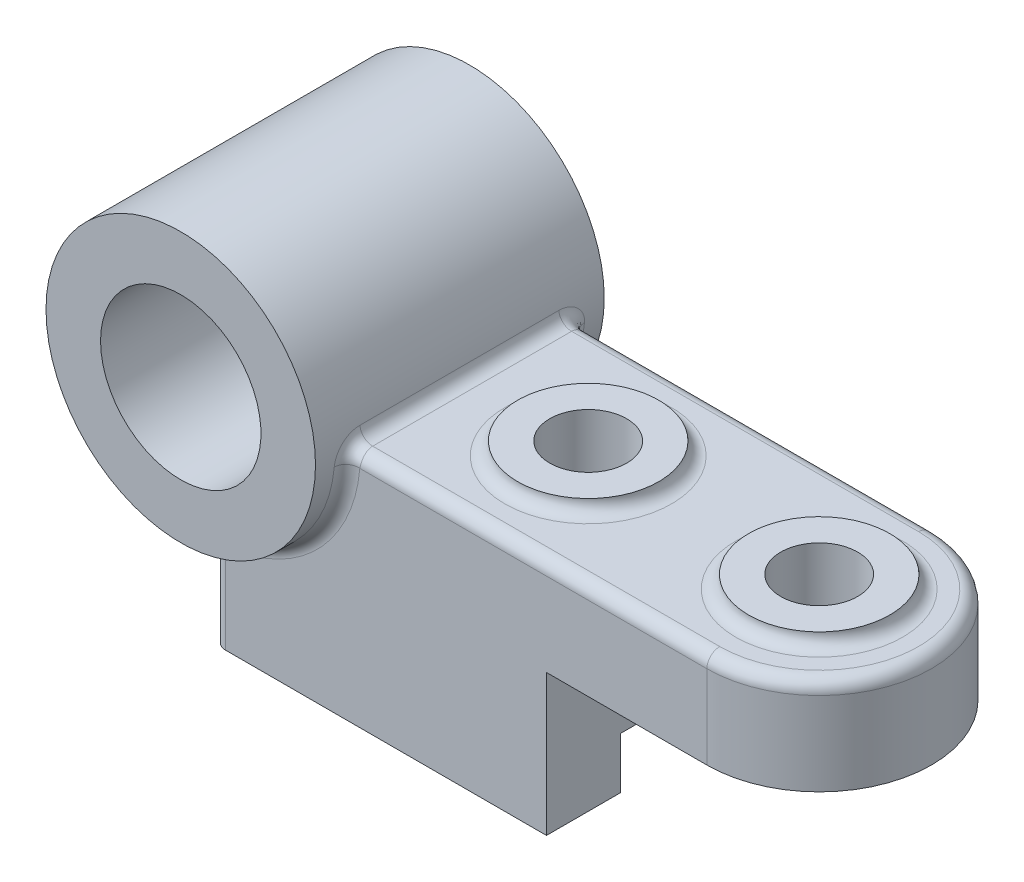
SolidWorks part; units mm, degrees
note: The reader was unsure of these and kept them because the rebuilt part matched: shared geometry of "Sketch1<3>", "Sketch2<3>".
ref_plane "Front Plane" through (0, 0, 0) normal (0, 0, 1) x (1, 0, 0)
ref_plane "Top Plane" through (0, 0, 0) normal (0, 1, 0) x (1, 0, 0)
ref_plane "Right Plane" through (0, 0, 0) normal (1, 0, 0) x (0, 0, -1)
sketch "Sketch1" plane through (0, 0, 0) normal (0, 0, 1) x (1, 0, 0)
  line L0 (0, -21) -> (0, -37)
  line L1 (0, -37) -> (52, -37)
  line L2 (52, -37) -> (52, -15)
  line L3 (52, -15) -> (94.5, -15)
  line L4 (21, 0) -> (94.5, 0)
  line L5 (94.5, 0) -> (94.5, -15)
  circle A0 centre (0, 0) radius 21
  circle A1 centre (0, 0) radius 12.5
  dimension "D1" = 42
  dimension "D2" = 25
  dimension "D3" = 15
  dimension "D4" = 52
  dimension "D5" = 37
  dimension "D6" = 94.5
extrude "Boss-Extrude1" add sketch "Sketch1" along normal mid plane 35 contours A0 L0 L1 L2 L3 L5 L4
extrude "Boss-Extrude2" add sketch "Sketch1<3>" along normal mid plane 45 contours A0 A1
sketch "Sketch1<3>" plane through (0, 0, 0) normal (0, 0, 1) x (1, 0, 0) same geometry as "Sketch1"
sketch "Sketch2" plane through (0, 0, 0) normal (0, 1, 0) x (1, 0, 0)
  line L0 (21, -22.5) -> (21, -17.5) construction
  line L1 (21, 17.5) -> (21, 22.5) construction
  line L2 (-21, 22.5) -> (-21, -22.5) construction
  line L3 (-21, -22.5) -> (21, -22.5) construction
  line L4 (94.5, 17.5) -> (21, 17.5)
  line L5 (21, 17.5) -> (21, -17.5)
  line L6 (21, -17.5) -> (94.5, -17.5)
  line L7 (94.5, -17.5) -> (94.5, 17.5)
  line L8 (94.5, 17.5) -> (21, 17.5)
  line L9 (21, 17.5) -> (21, -17.5)
  line L10 (21, -17.5) -> (94.5, -17.5)
  line L11 (94.5, -17.5) -> (94.5, 17.5)
  line L12 (21, 22.5) -> (-21, 22.5) construction
  line L13 (21, -22.5) -> (21, -17.5)
  line L14 (21, 17.5) -> (21, 22.5)
  line L15 (-21, 22.5) -> (-21, -22.5)
  line L16 (-21, -22.5) -> (21, -22.5)
  line L17 (21, 22.5) -> (-21, 22.5)
  arc A0 (77, -17.5) -> (77, 17.5) centre (77, 0) ccw
  circle A1 centre (77, 0) radius 11
  circle A2 centre (77, 0) radius 6
  circle A3 centre (41, 0) radius 11
  circle A4 centre (41, 0) radius 6
  point P12 (77, 6)
  line M8 (94.5, 17.5) -> (21, 17.5)
  line M11 (94.5, -17.5) -> (94.5, 17.5)
  dimension "D2" = 35
  dimension "D3" = 11.5
  dimension "D4" = 22
  dimension "D6" = 36
  dimension "D1" = 0
  dimension "D5" = 2
extrude "Cut-Extrude1" cut sketch "Sketch2" against normal blind 45 contours A0 L11 M8 | A0 L10 M11 | A2 | A4
extrude "Boss-Extrude3" add sketch "Sketch2<3>" along normal blind 2 contours A3 A4 | A1 A2
sketch "Sketch2<3>" plane through (0, 0, 0) normal (0, 1, 0) x (1, 0, 0) same geometry as "Sketch2"
fillet "Fillet1" radius 2 2 edges at (77, 0, 11) (41, 0, 11)
sketch "Sketch3" plane through (52, 0, 0) normal (1, 0, 0) x (0, 0, -1)
  line L0 (0, 0) -> (0, -37) construction
  line L1 (-17.5, -37) -> (17.5, -37) construction
  line L2 (-6, -29) -> (6, -29)
  line L3 (-6, -29) -> (-6, -37)
  line L4 (6, -29) -> (6, -37)
  line L5 (6, -37) -> (-6, -37)
  point P5 (6, -33)
  point P8 (0, -29)
  dimension "D1" = 8
  dimension "D2" = 12
extrude "Cut-Extrude2" cut sketch "Sketch3" against normal through all
fillet "Fillet2" radius 2 9 edges at (0, -29, 17.5) (0, -29, -17.5) (14.8492, -14.8492, -17.5) (0, -21, 0) (49, 0, -17.5) (94.5, 0, 0) (49, 0, 17.5) (14.8492, -14.8492, 17.5) (21, 0, 0)
